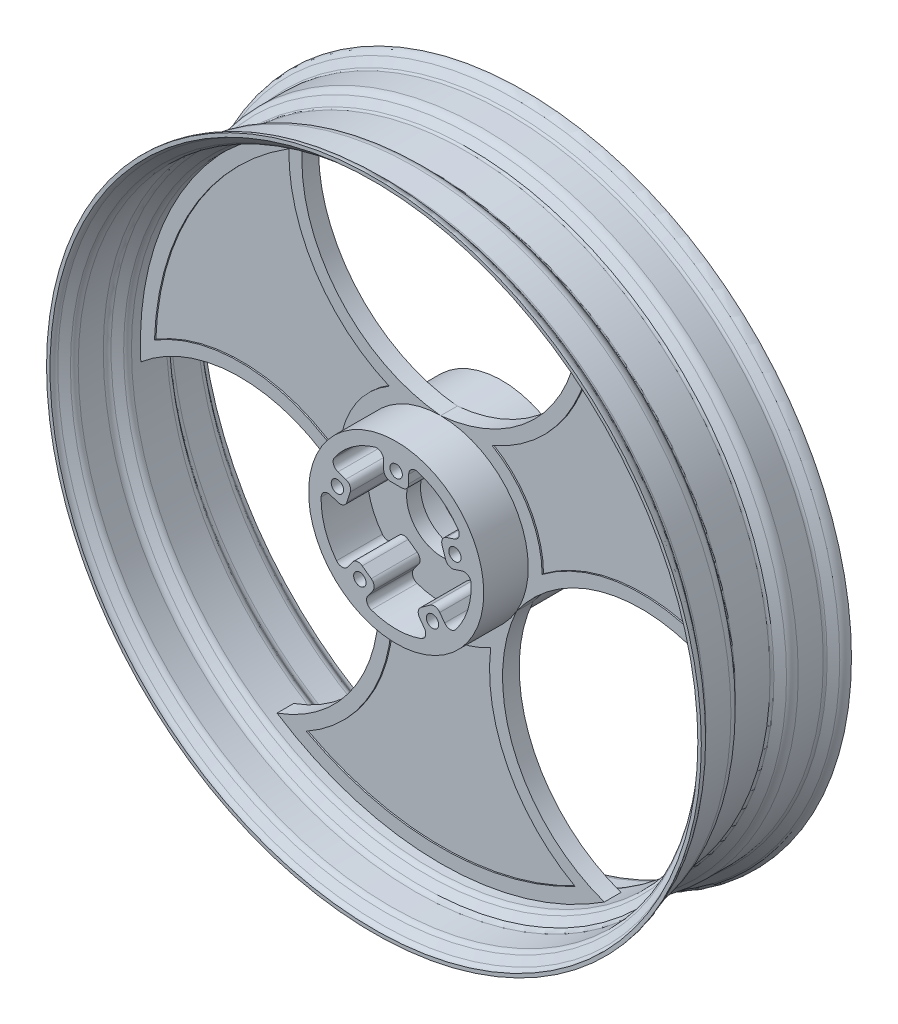
SolidWorks part; units mm, degrees
ref_plane "Front Plane" through (0, 0, 0) normal (0, 0, 1) x (1, 0, 0)
ref_plane "Top Plane" through (0, 0, 0) normal (0, 1, 0) x (1, 0, 0)
ref_plane "Right Plane" through (0, 0, 0) normal (1, 0, 0) x (0, 0, -1)
sketch "Sketch1" plane through (0, 0, 0) normal (1, 0, 0) x (0, 0, -1)
  line L0 (0, 106.096) -> (0, -87.6732) construction
  line L1 (-108.1057, 0) -> (149.1229, 0) construction
  line L27 (-38, 0) -> (38, 0)
  line L28 (38, 0) -> (38, 63)
  line L29 (-38, 0) -> (-38, 63)
  line L30 (38, 63) -> (6, 63)
  line L31 (-38, 63) -> (-6, 63)
  line L32 (6, 63) -> (6, 216)
  line L33 (-6, 63) -> (-6, 216)
  line L34 (6, 216) -> (12.4092, 216)
  line L35 (-6, 216) -> (-12.4092, 216)
  line L36 (16.2394, 217.7861) -> (20.3744, 222.7139)
  line L37 (-16.2394, 217.7861) -> (-20.3744, 222.7139)
  line L38 (24.2046, 224.5) -> (42.2046, 224.5)
  line L39 (-24.2046, 224.5) -> (-42.2046, 224.5)
  line L40 (46.0348, 226.2861) -> (50.1698, 231.2139)
  line L41 (-46.0348, 226.2861) -> (-50.1698, 231.2139)
  line L42 (54, 233) -> (54, 235.5)
  line L43 (-54, 233) -> (-54, 235.5)
  line L44 (48.2547, 232.8209) -> (44.1197, 227.893)
  line L45 (-48.2547, 232.8209) -> (-44.1197, 227.893)
  line L46 (42.2046, 227) -> (24.2046, 227)
  line L47 (-42.2046, 227) -> (-24.2046, 227)
  line L48 (18.4592, 224.3209) -> (14.3243, 219.393)
  line L49 (-18.4592, 224.3209) -> (-14.3243, 219.393)
  line L50 (12.4092, 218.5) -> (0, 218.5)
  line L51 (-12.4092, 218.5) -> (0, 218.5)
  arc A16 (12.4092, 216) -> (16.2394, 217.7861) centre (12.4092, 221) ccw
  arc A17 (-12.4092, 216) -> (-16.2394, 217.7861) centre (-12.4092, 221) cw
  arc A18 (20.3744, 222.7139) -> (24.2046, 224.5) centre (24.2046, 219.5) cw
  arc A19 (-20.3744, 222.7139) -> (-24.2046, 224.5) centre (-24.2046, 219.5) ccw
  arc A20 (42.2046, 224.5) -> (46.0348, 226.2861) centre (42.2046, 229.5) ccw
  arc A21 (-42.2046, 224.5) -> (-46.0348, 226.2861) centre (-42.2046, 229.5) cw
  arc A22 (50.1698, 231.2139) -> (54, 233) centre (54, 228) cw
  arc A23 (-50.1698, 231.2139) -> (-54, 233) centre (-54, 228) ccw
  arc A24 (54, 235.5) -> (48.2547, 232.8209) centre (54, 228) ccw
  arc A25 (-54, 235.5) -> (-48.2547, 232.8209) centre (-54, 228) cw
  arc A26 (44.1197, 227.893) -> (42.2046, 227) centre (42.2046, 229.5) cw
  arc A27 (-44.1197, 227.893) -> (-42.2046, 227) centre (-42.2046, 229.5) ccw
  arc A28 (24.2046, 227) -> (18.4592, 224.3209) centre (24.2046, 219.5) ccw
  arc A29 (-24.2046, 227) -> (-18.4592, 224.3209) centre (-24.2046, 219.5) cw
  arc A30 (14.3243, 219.393) -> (12.4092, 218.5) centre (12.4092, 221) cw
  arc A31 (-14.3243, 219.393) -> (-12.4092, 218.5) centre (-12.4092, 221) ccw
  point P8 (0, 0)
  dimension "D2" = 76
  dimension "D11" = 5
  dimension "D1" = 2.5
  dimension "D3" = 32
  dimension "D4" = 63
  dimension "D5" = 432
  dimension "D6" = 50
  dimension "D7" = 54
  dimension "D8" = 18
  dimension "D9" = 8.5
  dimension "D10" = 8.5
revolve "Revolve1" add sketch "Sketch1" angle 360 about L1
sketch "Sketch2" plane through (0, 0, 6) normal (0, 0, 1) x (1, 0, 0)
  line L0 (0, 0) -> (0, 315.672) construction
  arc A0 (0, 63) -> (98, 192.489) centre (-10.1738, 172.5285) ccw
  circle A1 centre (0, 0) radius 216 construction
  arc A2 (0, 63) -> (-98, 192.489) centre (10.1738, 172.5285) cw
  arc A3 (-98, 192.489) -> (98, 192.489) centre (0, 0) cw
  circle A4 centre (0, 0) radius 63 construction
  point P11 (0, 0)
  point P12 (0, 0)
  dimension "D1" = 110
  dimension "D2" = 196
extrude "Cut-Extrude1" cut sketch "Sketch2" against normal up to next contours A3 A0 A2
pattern_circular "CirPattern1" count 3 over 360 about axis through (0, 0, 108.1057) along (0, 0, 1) of "Cut-Extrude1" reverse direction yes
sketch "Sketch3" plane through (0, 0, 6) normal (0, 0, 1) x (1, 0, 0)
  line L0 (0, 0) -> (0, 318.5725) construction
  line L1 (0, 0) -> (-351.7619, 203.0898) construction
  line L2 (0, 0) -> (-372.0356, 12.9918) construction
  line L3 (0, 0) -> (-183.8421, 294.2089) construction
  arc A0 (-109.1634, 174.6979) -> (-205.8745, 7.1893) centre (0, 0) ccw
  arc A1 (-37.0383, 62.906) -> (-72.9973, 0.6231) centre (0, 0) ccw
  arc A2 (-109.1634, 174.6979) -> (-37.0383, 62.906) centre (10.1738, 172.5285) ccw
  arc A3 (-98, 192.489) -> (0, 63) centre (10.1738, 172.5285) ccw construction
  arc A4 (-205.8745, 7.1893) -> (-72.9973, 0.6231) centre (-144.3271, -95.0751) cw
  arc A5 (72.9973, 0.6231) -> (37.0383, 62.906) centre (0, 0) ccw
  arc A6 (109.1634, 174.6979) -> (37.0383, 62.906) centre (-10.1738, 172.5285) cw
  arc A7 (205.8745, 7.1893) -> (109.1634, 174.6979) centre (0, 0) ccw
  arc A8 (205.8745, 7.1893) -> (72.9973, 0.6231) centre (144.3271, -95.0751) ccw
  arc A9 (-35.9591, -63.5291) -> (35.9591, -63.5291) centre (0, 0) ccw
  arc A10 (96.7111, -181.8872) -> (35.9591, -63.5291) centre (154.501, -77.4534) cw
  arc A11 (-96.7111, -181.8872) -> (96.7111, -181.8872) centre (0, 0) ccw
  arc A12 (-96.7111, -181.8872) -> (-35.9591, -63.5291) centre (-154.501, -77.4534) ccw
  point P30 (0, 0)
  dimension "D4" = 412
  dimension "D5" = 146
  dimension "D1" = 60
  dimension "D2" = 28
  dimension "D3" = 3
extrude "Cut-Extrude2" cut sketch "Sketch3" against normal blind 1 contours A12 A11 A10 A9 | A8 A7 A6 A5 | A1 A4 A0 A2 region at (128.0484, 73.9288, 6) region at (0, -147.8575, 6)
mirror "Mirror1" about plane through (0, 0, 0) normal (0, 0, 1) of "Cut-Extrude2"
sketch "Sketch4" plane through (0, 0, 38) normal (0, 0, 1) x (1, 0, 0)
  circle A0 centre (0, 0) radius 54
  dimension "D1" = 108
extrude "Cut-Extrude3" cut sketch "Sketch4" against normal up to surface (33 mm away) up to face at (-117.5445, 67.8644, 5)
mirror "Mirror3" about plane through (0, 0, 0) normal (0, 0, 1) of "Cut-Extrude3"
sketch "Sketch5" plane through (0, 0, 5) normal (0, 0, 1) x (1, 0, 0)
  circle A0 centre (0, 0) radius 25.5
  dimension "D1" = 51
extrude "Cut-Extrude4" cut sketch "Sketch5" against normal through all
sketch "Sketch6" plane through (0, 0, 5) normal (0, 0, 1) x (1, 0, 0)
  line L0 (0, 0) -> (0, 131.9329) construction
  line L1 (0, 63) -> (0, 216) construction
  line L3 (-9, 36) -> (9, 36)
  line L4 (-9, 36) -> (-9, 53.2447)
  line L6 (9, 36) -> (9, 53.2447)
  line L7 (-9, 36) -> (9, 53.2447) construction
  line L8 (-9, 53.2447) -> (9, 36) construction
  circle A0 centre (0, 0) radius 54 construction
  circle A2 centre (0, 0) radius 54
  arc A3 (9, 53.2447) -> (-9, 53.2447) centre (0, 0) ccw
  point P5 (0, 44.6224)
  dimension "D1" = 36
  dimension "D2" = 18
  dimension "D3" = 0
extrude "Boss-Extrude1" add sketch "Sketch6" along normal up to surface (33 mm away) up to face at (54, 0, 38)
sketch "Sketch7" plane through (0, 0, 38) normal (0, 0, 1) x (1, 0, 0)
  line L0 (0, 0) -> (0, 63) construction
  circle A0 centre (0, 44.45) radius 4.45
  point P4 (0, 0)
  dimension "D2" = 8.9
  dimension "D1" = 44.45
extrude "Cut-Extrude5" cut sketch "Sketch7" against normal blind 25
pattern_circular "CirPattern2" count 5 over 360 about axis through (0, 0, -54) along (0, 0, 1) of "Cut-Extrude5", "Boss-Extrude1"
fillet "Fillet1" radius 5 20 edges at (24.0153, -48.3659, 21.5) (13.8791, -34.4147, 21.5) (38.5776, -37.7858, 21.5) (28.4414, -23.8345, 21.5) (-38.5776, -37.7858, 21.5) (-28.4414, -23.8345, 21.5) (-24.0153, -48.3659, 21.5) (-13.8791, -34.4147, 21.5) (53.4199, 7.894, 21.5) (37.0192, 2.5651, 21.5) (47.8576, 25.013, 21.5) (31.4569, 19.6841, 21.5) (9, 53.2447, 21.5) (9, 36, 21.5) (-9, 53.2447, 21.5) (-9, 36, 21.5) (-47.8576, 25.013, 21.5) (-31.4569, 19.6841, 21.5) (-53.4199, 7.894, 21.5) (-37.0192, 2.5651, 21.5)
